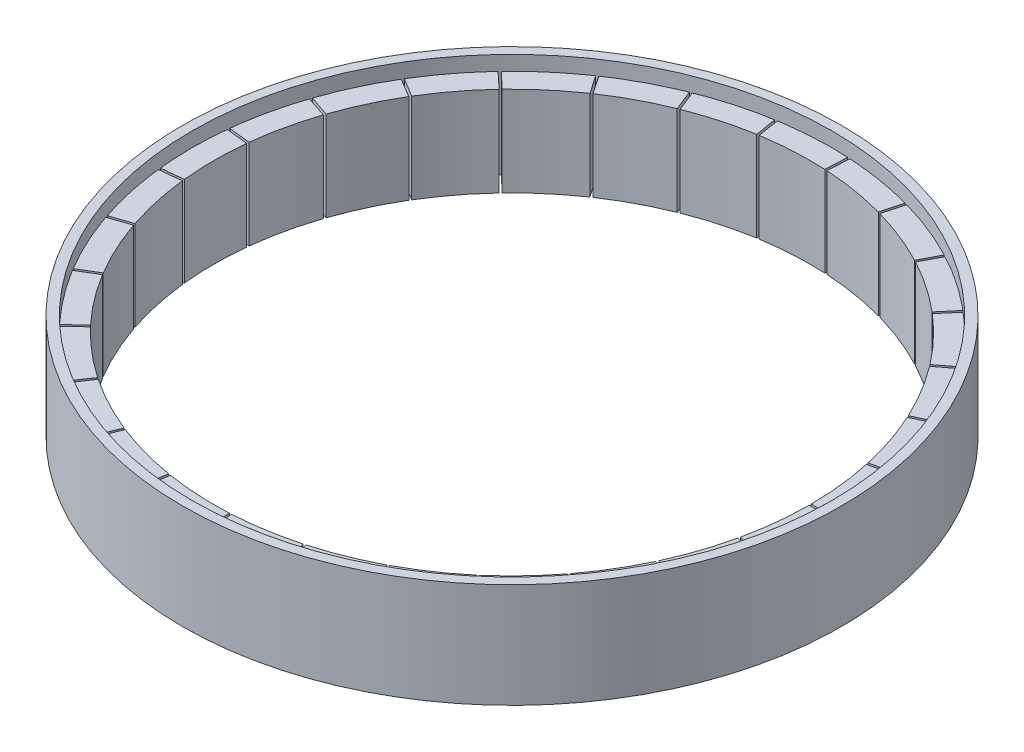
SolidWorks part; units mm, degrees
ref_plane "Front Plane" through (0, 0, 0) normal (0, 0, 1) x (1, 0, 0)
ref_plane "Top Plane" through (0, 0, 0) normal (0, 1, 0) x (1, 0, 0)
ref_plane "Right Plane" through (0, 0, 0) normal (1, 0, 0) x (0, 0, -1)
ref_axis "Axis1" through (0, 0, 0) along (0, 1, 0)
sketch "Sketch1" plane through (0, 0, 0) normal (0, 0, 1) x (1, 0, 0)
  line L0 (0, 0) -> (0, -37919.3043) construction
  line L2 (-45.1, 14.3) -> (-43.8, 14.3)
  line L3 (-45.1, 14.3) -> (-45.1, 0)
  line L4 (-45.1, 0) -> (-43.8, 0)
  line L5 (-43.8, 14.3) -> (-43.8, 0)
  dimension "D1" = 87.6
  dimension "D2" = 1.3
  dimension "D3" = 14.3
revolve "Revolve1" add sketch "Sketch1" angle 360 about L0
sketch "Sketch2" plane through (0, 0, 0) normal (0, 0, 1) x (1, 0, 0)
  line L0 (-45.1, 14.3) -> (-45.1, 0) construction
  line L1 (-40.8, 12.3) -> (-43.8, 12.3)
  line L2 (-40.8, 12.3) -> (-40.8, 0)
  line L3 (-40.8, 0) -> (-43.8, 0)
  line L4 (-43.8, 12.3) -> (-43.8, 0)
  line L5 (-45.1, 14.3) -> (-43.8, 14.3) construction
  dimension "D1" = 4.3
  dimension "D2" = 2
revolve "Revolve2" add sketch "Sketch2" angle 12 mid plane about axis through (0, 0, 0) along (0, 1, 0)
pattern_circular "CirPattern2" count 29 over 360 about axis through (0, 0, 0) along (0, 1, 0) of bodies 102
